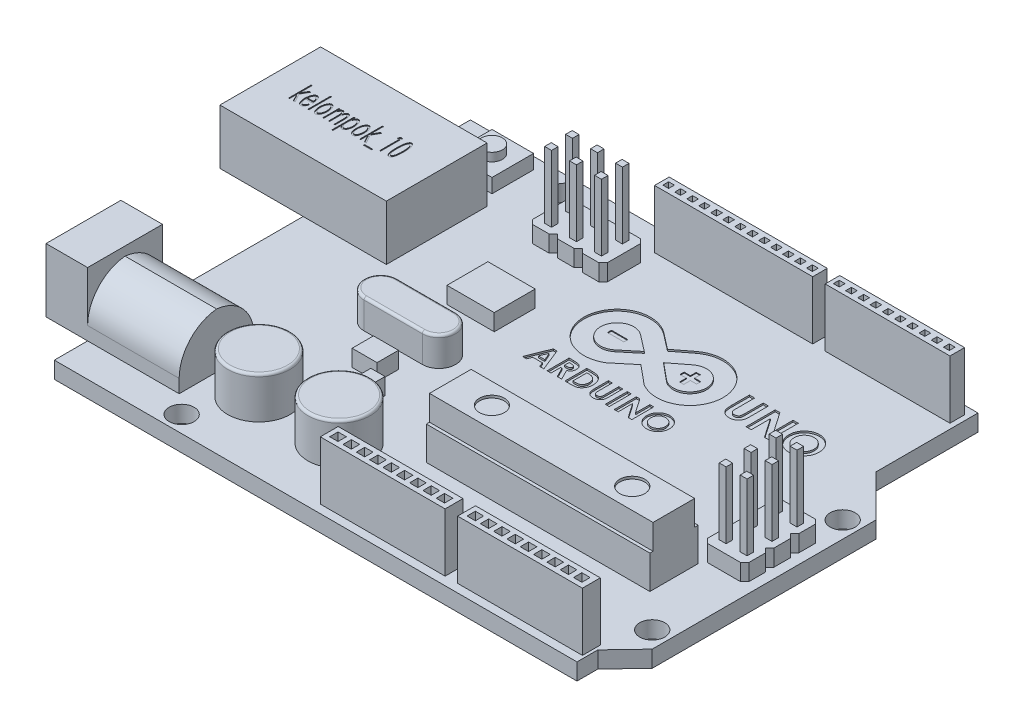
SolidWorks part; units mm, degrees
ref_plane "Front Plane" through (0, 0, 0) normal (0, 0, 1) x (1, 0, 0)
ref_plane "Top Plane" through (0, 0, 0) normal (0, 1, 0) x (1, 0, 0)
ref_plane "Right Plane" through (0, 0, 0) normal (1, 0, 0) x (0, 0, -1)
sketch "Sketch2" plane through (0, 0, 0) normal (0, 1, 0) x (1, 0, 0)
  line L0 (-33, 25) -> (33, -25) construction
  line L1 (-33, 25) -> (28, 25)
  line L2 (-33, 25) -> (-33, -25)
  line L3 (-33, -25) -> (29.8107, -25)
  line L4 (33, 7.74) -> (33, -19.15)
  line L5 (33, 25) -> (-33, -25) construction
  line L6 (28, 25) -> (28, 12.7479)
  line L7 (33, 7.74) -> (28, 12.7479)
  line L9 (29.8107, -25) -> (29.8107, -22.5)
  line L11 (33, -19.15) -> (29.8107, -22.5)
  dimension "D1" = 66
  dimension "D2" = 50
  dimension "D3" = 5
  dimension "D6" = 2.5
extrude "Boss-Extrude1" add sketch "Sketch2" along normal blind 2
sketch "Sketch3" plane through (0, 2, 0) normal (0, 1, 0) x (1, 0, 0)
  line L0 (28, 25) -> (-33, 25) construction
  line L1 (-33, 0) -> (33, 0) construction
  line L2 (-33, 25) -> (-33, -25) construction
  line L3 (33, -19.15) -> (33, 7.74) construction
  circle A0 centre (-19.7, 23) radius 1.5
  circle A1 centre (-19.7, -23) radius 1.5
  circle A2 centre (31, 5.74) radius 1.5
  circle A3 centre (31, -17.15) radius 1.5
  dimension "D1" = 3
  dimension "D2" = 2
  dimension "D4" = 3
  dimension "D5" = 2
  dimension "D6" = 2
  dimension "D7" = 3
  dimension "D3" = 13.3
  dimension "D8" = 2
extrude "Cut-Extrude2" cut sketch "Sketch3" against normal through all
sketch "Sketch4" plane through (0, 2, 0) normal (0, 1, 0) x (1, 0, 0)
  line L0 (-33, 25) -> (-33, -25) construction
  line L1 (-33, 17) -> (-23, 17)
  line L2 (-33, 17) -> (-33, 4.9)
  line L3 (-33, 4.9) -> (-23, 4.9)
  line L4 (-23, 17) -> (-23, 4.9)
  line L6 (-33, -12) -> (-22, -12)
  line L7 (-33, -12) -> (-33, -21)
  line L8 (-33, -21) -> (-22, -21)
  line L9 (-22, -12) -> (-22, -21)
  dimension "D1" = 8
  dimension "D2" = 12.1
  dimension "D3" = 10
  dimension "D4" = 4
  dimension "D5" = 9
  dimension "D6" = 11
extrude "Cut-Extrude3" cut sketch "Sketch4" against normal blind 0.4
sketch "Sketch5" plane through (0, 2, 0) normal (0, 1, 0) x (1, 0, 0)
  line L0 (27.2916, -0.8244) -> (26.7916, -0.3244)
  line L1 (31.2916, 2.1756) -> (27.2916, 2.1756)
  line L2 (31.7916, 1.6756) -> (31.7916, -0.3244)
  line L3 (31.2916, -0.8244) -> (27.2916, -0.8244)
  line L4 (26.7916, 1.6756) -> (26.7916, -0.3244)
  line L10 (27.2916, 2.1756) -> (26.7916, 1.6756)
  line L11 (31.2916, 2.1756) -> (31.7916, 1.6756)
  line L12 (31.2916, -0.8244) -> (31.7916, -0.3244)
extrude "Boss-Extrude2" add sketch "Sketch5" along normal blind 2
pattern_linear "LPattern1" count 3 spacing 3 along (0, 0, 1) of "Boss-Extrude2"
sketch "Sketch6" plane through (0, 4, 0) normal (0, 1, 0) x (1, 0, 0)
  line L1 (27.6416, 1.0456) -> (28.4716, 1.0456)
  line L2 (27.6416, 1.0456) -> (27.6416, 0.2556)
  line L3 (27.6416, 0.2556) -> (28.4716, 0.2556)
  line L4 (28.4716, 1.0456) -> (28.4716, 0.2556)
  dimension "D1" = 1.13
  dimension "D2" = 0.79
  dimension "D3" = 0.85
  dimension "D4" = 0.83
extrude "Boss-Extrude3" add sketch "Sketch6" along normal blind 8
pattern_linear "LPattern2" count 3 spacing 3 along (0, 0, 1) count 2 spacing 2.52 along (1, 0, 0) of "Boss-Extrude3"
sketch "Sketch7" plane through (0, 2, 0) normal (0, 1, 0) x (1, 0, 0)
  line L0 (28, 25) -> (-33, 25) construction
  line L1 (-16.41, 20.86) -> (-14.41, 20.86)
  line L2 (-16.91, 20.36) -> (-16.91, 16.36)
  line L3 (-16.41, 15.86) -> (-14.41, 15.86)
  line L4 (-13.91, 20.36) -> (-13.91, 16.36)
  line L5 (-33, 25) -> (-33, 17) construction
  line L6 (-13.91, 20.86) -> (-14.0975, 20.5475) construction
  line L7 (-16.91, 20.86) -> (-16.7225, 20.5475) construction
  line L10 (-16.41, 20.86) -> (-16.91, 20.36)
  line L11 (-14.41, 20.86) -> (-13.91, 20.36)
  line L12 (-16.41, 15.86) -> (-16.91, 16.36)
  line L13 (-14.41, 15.86) -> (-13.91, 16.36)
  line L14 (-14.0975, 16.1725) -> (-13.91, 15.86) construction
  line L15 (-16.7225, 16.1725) -> (-16.91, 15.86) construction
  point P6 (-16.91, 18.36)
  dimension "D1" = 4.14
  dimension "D2" = 16.09
  dimension "D3" = 3
  dimension "D4" = 5
  dimension "D5" = 0.5
  dimension "D6" = 0.5
extrude "Boss-Extrude4" add sketch "Sketch7" along normal blind 2
pattern_linear "LPattern3" count 3 spacing 3 along (1, 0, 0) of "Boss-Extrude4"
sketch "Sketch8" plane through (0, 4, 0) normal (0, 1, 0) x (1, 0, 0)
  line L0 (-14.41, 20.86) -> (-16.41, 20.86) construction
  line L1 (-15.78, 20.01) -> (-14.95, 20.01)
  line L2 (-15.78, 20.01) -> (-15.78, 19.22)
  line L3 (-15.78, 19.22) -> (-14.95, 19.22)
  line L4 (-14.95, 20.01) -> (-14.95, 19.22)
  line L5 (-16.91, 20.36) -> (-16.91, 16.36) construction
  dimension "D1" = 0.85
  dimension "D2" = 1.13
  dimension "D3" = 0.79
  dimension "D4" = 0.83
extrude "Boss-Extrude5" add sketch "Sketch8" along normal blind 8
pattern_linear "LPattern4" count 3 spacing 3 along (1, 0, 0) count 2 spacing 2.52 along (0, 0, 1) of "Boss-Extrude5"
sketch "Sketch13" plane through (0, 2, 0) normal (0, 1, 0) x (1, 0, 0)
  line L0 (-17.4291, -1.3426) -> (-10.4291, -1.3426) construction
  line L4 (-17.4291, 0.6574) -> (-10.4291, 0.6574)
  line L5 (-17.4291, -3.3426) -> (-10.4291, -3.3426)
  arc A2 (-17.4291, 0.6574) -> (-17.4291, -3.3426) centre (-17.4291, -1.3426) ccw
  arc A3 (-10.4291, -3.3426) -> (-10.4291, 0.6574) centre (-10.4291, -1.3426) ccw
  point P2 (-13.9291, -1.3426)
  dimension "D1" = 7
  dimension "D2" = 2
extrude "Boss-Extrude6" add sketch "Sketch13" along normal blind 3.5
fillet "Fillet4" radius 0.3 4 edges at (-19.4291, 5.5, 1.3426) (-13.9291, 5.5, -0.6574) (-8.4291, 5.5, 1.3426) (-13.9291, 5.5, 3.3426)
sketch "Sketch15" plane through (0, 2, 0) normal (0, 1, 0) x (1, 0, 0)
  line L1 (-15.1968, 9.2986) -> (-9.5153, 9.2986)
  line L2 (-15.1968, 9.2986) -> (-15.1968, 4.382)
  line L3 (-15.1968, 4.382) -> (-9.5153, 4.382)
  line L4 (-9.5153, 9.2986) -> (-9.5153, 4.382)
extrude "Boss-Extrude8" add sketch "Sketch15" along normal blind 2
sketch "Sketch17" plane through (0, 2, 0) normal (0, 1, 0) x (1, 0, 0)
  line L1 (-14.3468, -5.2998) -> (-11.349, -5.2998)
  line L2 (-14.3468, -5.2998) -> (-14.3468, -7.8693)
  line L3 (-14.3468, -7.8693) -> (-11.349, -7.8693)
  line L4 (-11.349, -5.2998) -> (-11.349, -7.8693)
extrude "Boss-Extrude9" add sketch "Sketch17" along normal blind 2
sketch "Sketch18" plane through (0, 2, 0) normal (0, 1, 0) x (1, 0, 0)
  line L1 (-11.1349, -8.8329) -> (-9.4218, -8.8329)
  line L2 (-11.1349, -8.8329) -> (-11.1349, -11.6167)
  line L3 (-11.1349, -11.6167) -> (-9.4218, -11.6167)
  line L4 (-9.4218, -8.8329) -> (-9.4218, -11.6167)
extrude "Boss-Extrude10" add sketch "Sketch18" along normal blind 2
sketch "Sketch20" plane through (0, 2, 0) normal (0, 1, 0) x (1, 0, 0)
  line L1 (-29.0149, 18.6084) -> (-24.0149, 18.6084)
  line L2 (-29.0149, 18.6084) -> (-29.0149, 23.6084)
  line L3 (-29.0149, 23.6084) -> (-24.0149, 23.6084)
  line L4 (-24.0149, 18.6084) -> (-24.0149, 23.6084)
  dimension "D1" = 5
  dimension "D2" = 5
extrude "Boss-Extrude11" add sketch "Sketch20" along normal blind 1.7
sketch "Sketch22" plane through (0, 3.7, 0) normal (0, 1, 0) x (1, 0, 0)
  line L0 (-29.0149, 21.1084) -> (-24.0149, 21.1084) construction
  line L1 (-29.0149, 23.6084) -> (-29.0149, 18.6084) construction
  line L2 (-24.0149, 18.6084) -> (-24.0149, 23.6084) construction
  circle A0 centre (-26.5149, 21.1084) radius 1.25
  dimension "D1" = 2.5
extrude "Boss-Extrude12" add sketch "Sketch22" along normal blind 1
sketch "Sketch23" plane through (0, 2, 0) normal (0, 1, 0) x (1, 0, 0)
  circle A0 centre (-16.9164, -16.5) radius 3.75
  dimension "D1" = 7.5
extrude "Boss-Extrude13" add sketch "Sketch23" along normal blind 5
sketch "Sketch24" plane through (0, 2, 0) normal (0, 1, 0) x (1, 0, 0)
  circle A0 centre (-7.2805, -16.5) radius 3.75
  dimension "D1" = 7.5
extrude "Boss-Extrude14" add sketch "Sketch24" along normal blind 5
fillet "Fillet5" radius 0.3 1 edges at (-7.2805, 7, 20.25)
fillet "Fillet6" radius 0.3 1 edges at (-16.9164, 7, 20.25)
sketch "Sketch25" plane through (0, 2, 0) normal (0, 1, 0) x (1, 0, 0)
  line L0 (-33, -25) -> (29.8107, -25) construction
  line L10 (-2.0383, -21.85) -> (12.9617, -21.85)
  line L11 (-2.0383, -21.85) -> (-2.0383, -24)
  line L12 (-2.0383, -24) -> (12.9617, -24)
  line L13 (12.9617, -21.85) -> (12.9617, -24)
  line L14 (14.4617, -21.85) -> (29.4617, -21.85)
  line L15 (14.4617, -21.85) -> (14.4617, -24)
  line L16 (14.4617, -24) -> (29.4617, -24)
  line L17 (29.4617, -21.85) -> (29.4617, -24)
  line L18 (12.3839, 24) -> (27.3839, 24)
  line L19 (-8.1161, 24) -> (10.8839, 24)
  line L20 (-8.1161, 24) -> (-8.1161, 22.2484)
  line L21 (-8.1161, 22.2484) -> (10.8839, 22.2484)
  line L22 (10.8839, 24) -> (10.8839, 22.2484)
  line L23 (12.3839, 24) -> (12.3839, 22.2484)
  line L24 (12.3839, 22.2484) -> (27.3839, 22.2484)
  line L25 (27.3839, 24) -> (27.3839, 22.2484)
  line L26 (28, 25) -> (-33, 25) construction
  dimension "D1" = 15
  dimension "D2" = 15
  dimension "D3" = 2.15
  dimension "D4" = 2.15
  dimension "D5" = 1.5
  dimension "D6" = 19
  dimension "D7" = 15
  dimension "D8" = 1
  dimension "D9" = 1
  dimension "D10" = 1
  dimension "D11" = 1.5
sketch "Sketch27" plane through (0, 2, 0) normal (0, 1, 0) x (1, 0, 0)
  line L0 (5.8645, 12.8775) -> (3.8851, 11.3504)
  line L1 (3.8851, 11.3504) -> (5.8095, 9.7545)
  line L2 (4.6428, 14.461) -> (2.7154, 12.9739)
  line L3 (2.7154, 9.774) -> (4.992, 7.886)
  line L7 (1.5456, 11.3504) -> (-0.3788, 9.7545)
  line L8 (-0.4338, 12.8775) -> (1.5456, 11.3504)
  line L10 (0.7879, 14.461) -> (2.7154, 12.9739)
  line L11 (2.7154, 9.774) -> (0.4387, 7.886)
  arc A0 (5.8095, 9.7545) -> (5.8645, 12.8775) centre (7.0862, 11.294) ccw
  arc A2 (4.992, 7.886) -> (4.6428, 14.461) centre (7.0862, 11.294) ccw
  arc A3 (-0.3788, 9.7545) -> (-0.4338, 12.8775) centre (-1.6555, 11.294) cw
  arc A4 (0.4387, 7.886) -> (0.7879, 14.461) centre (-1.6555, 11.294) cw
  text T0 "<b>ARDUINO</b>" font "Century Gothic" height in points 10
  point P2 (-5.6498, 11.5062)
  dimension "D1" = 4
  dimension "D2" = 2
  dimension "D3" = 2.5
  dimension "D4" = 2.5
  dimension "D5" = 8
extrude "Cut-Extrude5" cut sketch "Sketch27" against normal blind 0.2
sketch "Sketch29" plane through (0, 2, 0) normal (0, 1, 0) x (1, 0, 0)
  text T0 "<b>UNO</b>\r\n"
extrude "Cut-Extrude6" cut sketch "Sketch29" against normal blind 0.2
sketch "Sketch30" plane through (0, 2, 0) normal (0, 1, 0) x (1, 0, 0)
  line L1 (6.8413, 12.294) -> (7.3413, 12.294)
  line L2 (6.8413, 12.294) -> (6.8413, 11.6007)
  line L3 (6.8413, 10.294) -> (7.3413, 10.294)
  line L4 (7.3413, 12.294) -> (7.3413, 11.6007)
  line L5 (6.0863, 11.6007) -> (6.8413, 11.6007)
  line L6 (6.0863, 11.6007) -> (6.0863, 11.1007)
  line L7 (6.0863, 11.1007) -> (6.8413, 11.1007)
  line L8 (8.0863, 11.6007) -> (8.0863, 11.1007)
  line L9 (-2.6354, 11.5921) -> (-0.6721, 11.5921)
  line L10 (-2.6354, 11.5921) -> (-2.6354, 11.1188)
  line L11 (-2.6354, 11.1188) -> (-0.6721, 11.1188)
  line L12 (-0.6721, 11.5921) -> (-0.6721, 11.1188)
  line L13 (7.3413, 11.1007) -> (8.0863, 11.1007)
  line L14 (6.8413, 11.1007) -> (6.8413, 10.294)
  line L15 (7.3413, 11.1007) -> (7.3413, 10.294)
  line L17 (7.3413, 11.6007) -> (8.0863, 11.6007)
  dimension "D1" = 0.5
  dimension "D2" = 0.5
  dimension "D5" = 2
extrude "Cut-Extrude7" cut sketch "Sketch30" against normal blind 0.1
sketch "Sketch33" plane through (0, 1.6, 0) normal (0, 1, 0) x (1, 0, 0)
  line L1 (-33, 17) -> (-23, 17)
  line L2 (-33, 17) -> (-33, 4.9)
  line L3 (-33, 4.9) -> (-23, 4.9)
  line L4 (-23, 17) -> (-23, 4.9)
extrude "Boss-Extrude17" add sketch "Sketch33" along normal blind 7 contours L2 L1 L4 L3
sketch "Sketch35" plane through (-33, 0, 0) normal (-1, 0, 0) x (0, 0, 1)
  line L1 (-17, 8.6) -> (-4.9, 8.6)
  line L2 (-17, 8.6) -> (-17, 2)
  line L3 (-17, 2) -> (-4.9, 2)
  line L4 (-4.9, 8.6) -> (-4.9, 2)
extrude "Boss-Extrude18" add sketch "Sketch35" along normal blind 10
sketch "Sketch36" plane through (0, 1.6, 0) normal (0, 1, 0) x (1, 0, 0)
  line L1 (-33, -12) -> (-22, -12)
  line L2 (-33, -12) -> (-33, -21)
  line L3 (-33, -21) -> (-22, -21)
  line L4 (-22, -12) -> (-22, -21)
extrude "Boss-Extrude19" add sketch "Sketch36" along normal blind 7
sketch "Sketch37" plane through (-33, 0, 0) normal (-1, 0, 0) x (0, 0, 1)
  line L1 (12, 2) -> (21, 2)
  line L2 (12, 2) -> (12, 8.6)
  line L3 (12, 8.6) -> (21, 8.6)
  line L4 (21, 2) -> (21, 8.6)
extrude "Boss-Extrude20" add sketch "Sketch37" against normal blind 1
fillet "Fillet8" radius 5 2 edges at (-27.5, 8.6, 12) (-27.5, 8.6, 21)
sketch "Sketch47" plane through (-33, 0, 0) normal (-1, 0, 0) x (0, 0, 1)
  line L0 (21, 3.6) -> (21, 2) construction
  line L1 (12, 2) -> (21, 2)
  line L2 (12, 2) -> (12, 9.6357)
  line L3 (12, 9.6357) -> (21, 9.6357)
  line L4 (21, 2) -> (21, 9.6357)
extrude "Boss-Extrude23" add sketch "Sketch47" along normal blind 5
sketch "Sketch48" plane through (-38, 0, 0) normal (-1, 0, 0) x (0, 0, 1)
  circle A0 centre (16.5, 5.8178) radius 2.6874
extrude "Cut-Extrude14" cut sketch "Sketch48" against normal blind 8
sketch "Sketch49" plane through (-30, 0, 0) normal (-1, 0, 0) x (0, 0, 1)
  circle A0 centre (16.5, 5.8178) radius 0.2092
extrude "Boss-Extrude24" add sketch "Sketch49" along normal blind 5.5
fillet "Fillet16" radius 0.1 1 edges at (-35.5, 5.8178, 16.7092)
sketch "Sketch54" plane through (-43, 0, 0) normal (-1, 0, 0) x (0, 0, 1)
  line L0 (-14.5, 6.4502) -> (-13.4359, 7.7502)
  line L2 (-14.5, 6.4502) -> (-14.5, 3.0635)
  line L3 (-14.5, 3.0635) -> (-7.4, 3.0635)
  line L4 (-7.4, 6.4502) -> (-7.4, 3.0635)
  line L5 (-13.4359, 7.7502) -> (-8.4359, 7.7502)
  line L6 (-8.4359, 7.7502) -> (-7.4, 6.4502)
  line L7 (-17, 8.6) -> (-17, 2) construction
  line L8 (-4.9, 2) -> (-4.9, 8.6) construction
  dimension "D1" = 2.5
  dimension "D2" = 2.5
  dimension "D4" = 5
  dimension "D5" = 1.68
extrude "Cut-Extrude15" cut sketch "Sketch54" against normal blind 6
sketch "Sketch55" plane through (-37, 0, 0) normal (-1, 0, 0) x (0, 0, 1)
  line L0 (-14.5, 6.4502) -> (-14.5, 3.0635) construction
  line L1 (-12.4955, 5.6822) -> (-9.4, 5.6822)
  line L2 (-12.4955, 5.6822) -> (-12.4955, 4.7075)
  line L3 (-12.4955, 4.7075) -> (-9.4, 4.7075)
  line L4 (-9.4, 5.6822) -> (-9.4, 4.7075)
  line L5 (-7.4, 3.0635) -> (-7.4, 6.4502) construction
  dimension "D1" = 2.0045
  dimension "D2" = 2
extrude "Boss-Extrude25" add sketch "Sketch55" along normal blind 6
extrude "Boss-Extrude26" add sketch "Sketch25" along normal blind 7
sketch "Sketch57" plane through (0, 9, 0) normal (0, 1, 0) x (1, 0, 0)
  line L0 (-6.214, 23.4742) -> (-6.214, 22.7742)
  line L1 (-7.654, 23.4742) -> (-6.954, 23.4742)
  line L2 (-7.654, 23.4742) -> (-7.654, 22.7742)
  line L3 (-7.654, 22.7742) -> (-6.954, 22.7742)
  line L4 (-6.954, 23.4742) -> (-6.954, 22.7742)
  line L5 (-6.214, 23.4742) -> (-5.514, 23.4742)
  line L6 (-5.514, 23.4742) -> (-5.514, 22.7742)
  line L7 (-6.214, 22.7742) -> (-5.514, 22.7742)
  line L8 (-4.774, 23.4742) -> (-4.774, 22.7742)
  line L9 (-4.774, 23.4742) -> (-4.074, 23.4742)
  line L10 (-4.074, 23.4742) -> (-4.074, 22.7742)
  line L11 (-4.774, 22.7742) -> (-4.074, 22.7742)
  line L12 (-3.334, 23.4742) -> (-3.334, 22.7742)
  line L13 (-3.334, 23.4742) -> (-2.634, 23.4742)
  line L14 (-2.634, 23.4742) -> (-2.634, 22.7742)
  line L15 (-3.334, 22.7742) -> (-2.634, 22.7742)
  line L16 (-1.894, 23.4742) -> (-1.894, 22.7742)
  line L17 (-1.894, 23.4742) -> (-1.194, 23.4742)
  line L18 (-1.194, 23.4742) -> (-1.194, 22.7742)
  line L19 (-1.894, 22.7742) -> (-1.194, 22.7742)
  line L20 (-0.454, 23.4742) -> (-0.454, 22.7742)
  line L21 (-0.454, 23.4742) -> (0.246, 23.4742)
  line L22 (0.246, 23.4742) -> (0.246, 22.7742)
  line L23 (-0.454, 22.7742) -> (0.246, 22.7742)
  line L24 (0.986, 23.4742) -> (0.986, 22.7742)
  line L25 (0.986, 23.4742) -> (1.686, 23.4742)
  line L26 (1.686, 23.4742) -> (1.686, 22.7742)
  line L27 (0.986, 22.7742) -> (1.686, 22.7742)
  line L28 (2.426, 23.4742) -> (2.426, 22.7742)
  line L29 (2.426, 23.4742) -> (3.126, 23.4742)
  line L30 (3.126, 23.4742) -> (3.126, 22.7742)
  line L31 (2.426, 22.7742) -> (3.126, 22.7742)
  line L32 (3.866, 23.4742) -> (3.866, 22.7742)
  line L33 (3.866, 23.4742) -> (4.566, 23.4742)
  line L34 (4.566, 23.4742) -> (4.566, 22.7742)
  line L35 (3.866, 22.7742) -> (4.566, 22.7742)
  line L36 (5.306, 23.4742) -> (5.306, 22.7742)
  line L37 (5.306, 23.4742) -> (6.006, 23.4742)
  line L38 (6.006, 23.4742) -> (6.006, 22.7742)
  line L39 (5.306, 22.7742) -> (6.006, 22.7742)
  line L40 (6.746, 23.4742) -> (6.746, 22.7742)
  line L41 (6.746, 23.4742) -> (7.446, 23.4742)
  line L42 (7.446, 23.4742) -> (7.446, 22.7742)
  line L43 (6.746, 22.7742) -> (7.446, 22.7742)
  line L44 (8.186, 23.4742) -> (8.186, 22.7742)
  line L45 (8.186, 23.4742) -> (8.886, 23.4742)
  line L46 (8.886, 23.4742) -> (8.886, 22.7742)
  line L47 (8.186, 22.7742) -> (8.886, 22.7742)
  line L48 (9.626, 23.4742) -> (9.626, 22.7742)
  line L49 (9.626, 23.4742) -> (10.326, 23.4742)
  line L50 (10.326, 23.4742) -> (10.326, 22.7742)
  line L51 (9.626, 22.7742) -> (10.326, 22.7742)
  dimension "D1" = 0.7
  dimension "D2" = 0.7
  dimension "D3" = 0.7
  dimension "D4" = 0.7
  dimension "D5" = 13
extrude "Cut-Extrude17" cut sketch "Sketch57" against normal blind 6
sketch "Sketch58" plane through (0, 9, 0) normal (0, 1, 0) x (1, 0, 0)
  line L0 (14.316, 23.4742) -> (14.316, 22.7742)
  line L1 (12.846, 23.4742) -> (13.546, 23.4742)
  line L2 (12.846, 23.4742) -> (12.846, 22.7742)
  line L3 (12.846, 22.7742) -> (13.546, 22.7742)
  line L4 (13.546, 23.4742) -> (13.546, 22.7742)
  line L5 (14.316, 23.4742) -> (15.016, 23.4742)
  line L6 (15.016, 23.4742) -> (15.016, 22.7742)
  line L7 (14.316, 22.7742) -> (15.016, 22.7742)
  line L8 (15.786, 23.4742) -> (15.786, 22.7742)
  line L9 (15.786, 23.4742) -> (16.486, 23.4742)
  line L10 (16.486, 23.4742) -> (16.486, 22.7742)
  line L11 (15.786, 22.7742) -> (16.486, 22.7742)
  line L12 (17.256, 23.4742) -> (17.256, 22.7742)
  line L13 (17.256, 23.4742) -> (17.956, 23.4742)
  line L14 (17.956, 23.4742) -> (17.956, 22.7742)
  line L15 (17.256, 22.7742) -> (17.956, 22.7742)
  line L16 (18.726, 23.4742) -> (18.726, 22.7742)
  line L17 (18.726, 23.4742) -> (19.426, 23.4742)
  line L18 (19.426, 23.4742) -> (19.426, 22.7742)
  line L19 (18.726, 22.7742) -> (19.426, 22.7742)
  line L20 (20.196, 23.4742) -> (20.196, 22.7742)
  line L21 (20.196, 23.4742) -> (20.896, 23.4742)
  line L22 (20.896, 23.4742) -> (20.896, 22.7742)
  line L23 (20.196, 22.7742) -> (20.896, 22.7742)
  line L24 (21.666, 23.4742) -> (21.666, 22.7742)
  line L25 (21.666, 23.4742) -> (22.366, 23.4742)
  line L26 (22.366, 23.4742) -> (22.366, 22.7742)
  line L27 (21.666, 22.7742) -> (22.366, 22.7742)
  line L28 (23.136, 23.4742) -> (23.136, 22.7742)
  line L29 (23.136, 23.4742) -> (23.836, 23.4742)
  line L30 (23.836, 23.4742) -> (23.836, 22.7742)
  line L31 (23.136, 22.7742) -> (23.836, 22.7742)
  line L32 (24.606, 23.4742) -> (24.606, 22.7742)
  line L33 (24.606, 23.4742) -> (25.306, 23.4742)
  line L34 (25.306, 23.4742) -> (25.306, 22.7742)
  line L35 (24.606, 22.7742) -> (25.306, 22.7742)
  line L36 (26.076, 23.4742) -> (26.076, 22.7742)
  line L37 (26.076, 23.4742) -> (26.776, 23.4742)
  line L38 (26.776, 23.4742) -> (26.776, 22.7742)
  line L39 (26.076, 22.7742) -> (26.776, 22.7742)
  dimension "D1" = 0.7
  dimension "D2" = 0.7
  dimension "D3" = 0.7
  dimension "D4" = 0.7
  dimension "D5" = 10
extrude "Cut-Extrude18" cut sketch "Sketch58" against normal blind 6
sketch "Sketch59" plane through (0, 9, 0) normal (0, 1, 0) x (1, 0, 0)
  line L0 (0.118, -22.425) -> (0.118, -23.425)
  line L1 (-1.482, -22.425) -> (-0.482, -22.425)
  line L2 (-1.482, -22.425) -> (-1.482, -23.425)
  line L3 (-1.482, -23.425) -> (-0.482, -23.425)
  line L4 (-0.482, -22.425) -> (-0.482, -23.425)
  line L5 (0.118, -22.425) -> (1.118, -22.425)
  line L6 (1.118, -22.425) -> (1.118, -23.425)
  line L7 (0.118, -23.425) -> (1.118, -23.425)
  line L8 (1.718, -22.425) -> (1.718, -23.425)
  line L9 (1.718, -22.425) -> (2.718, -22.425)
  line L10 (2.718, -22.425) -> (2.718, -23.425)
  line L11 (1.718, -23.425) -> (2.718, -23.425)
  line L12 (3.318, -22.425) -> (3.318, -23.425)
  line L13 (3.318, -22.425) -> (4.318, -22.425)
  line L14 (4.318, -22.425) -> (4.318, -23.425)
  line L15 (3.318, -23.425) -> (4.318, -23.425)
  line L16 (4.918, -22.425) -> (4.918, -23.425)
  line L17 (4.918, -22.425) -> (5.918, -22.425)
  line L18 (5.918, -22.425) -> (5.918, -23.425)
  line L19 (4.918, -23.425) -> (5.918, -23.425)
  line L20 (6.518, -22.425) -> (6.518, -23.425)
  line L21 (6.518, -22.425) -> (7.518, -22.425)
  line L22 (7.518, -22.425) -> (7.518, -23.425)
  line L23 (6.518, -23.425) -> (7.518, -23.425)
  line L24 (8.118, -22.425) -> (8.118, -23.425)
  line L25 (8.118, -22.425) -> (9.118, -22.425)
  line L26 (9.118, -22.425) -> (9.118, -23.425)
  line L27 (8.118, -23.425) -> (9.118, -23.425)
  line L28 (9.718, -22.425) -> (9.718, -23.425)
  line L29 (9.718, -22.425) -> (10.718, -22.425)
  line L30 (10.718, -22.425) -> (10.718, -23.425)
  line L31 (9.718, -23.425) -> (10.718, -23.425)
  line L32 (11.318, -22.425) -> (11.318, -23.425)
  line L33 (11.318, -22.425) -> (12.318, -22.425)
  line L34 (12.318, -22.425) -> (12.318, -23.425)
  line L35 (11.318, -23.425) -> (12.318, -23.425)
  dimension "D1" = 0.8
  dimension "D2" = 0.8
  dimension "D3" = 1
  dimension "D4" = 1
  dimension "D5" = 9
extrude "Cut-Extrude19" cut sketch "Sketch59" against normal blind 6
sketch "Sketch60" plane through (0, 9, 0) normal (0, 1, 0) x (1, 0, 0)
  line L0 (16.618, -22.425) -> (16.618, -23.425)
  line L1 (15.018, -22.425) -> (16.018, -22.425)
  line L2 (15.018, -22.425) -> (15.018, -23.425)
  line L3 (15.018, -23.425) -> (16.018, -23.425)
  line L4 (16.018, -22.425) -> (16.018, -23.425)
  line L5 (16.618, -22.425) -> (17.618, -22.425)
  line L6 (17.618, -22.425) -> (17.618, -23.425)
  line L7 (16.618, -23.425) -> (17.618, -23.425)
  line L8 (18.218, -22.425) -> (18.218, -23.425)
  line L9 (18.218, -22.425) -> (19.218, -22.425)
  line L10 (19.218, -22.425) -> (19.218, -23.425)
  line L11 (18.218, -23.425) -> (19.218, -23.425)
  line L12 (19.818, -22.425) -> (19.818, -23.425)
  line L13 (19.818, -22.425) -> (20.818, -22.425)
  line L14 (20.818, -22.425) -> (20.818, -23.425)
  line L15 (19.818, -23.425) -> (20.818, -23.425)
  line L16 (21.418, -22.425) -> (21.418, -23.425)
  line L17 (21.418, -22.425) -> (22.418, -22.425)
  line L18 (22.418, -22.425) -> (22.418, -23.425)
  line L19 (21.418, -23.425) -> (22.418, -23.425)
  line L20 (23.018, -22.425) -> (23.018, -23.425)
  line L21 (23.018, -22.425) -> (24.018, -22.425)
  line L22 (24.018, -22.425) -> (24.018, -23.425)
  line L23 (23.018, -23.425) -> (24.018, -23.425)
  line L24 (24.618, -22.425) -> (24.618, -23.425)
  line L25 (24.618, -22.425) -> (25.618, -22.425)
  line L26 (25.618, -22.425) -> (25.618, -23.425)
  line L27 (24.618, -23.425) -> (25.618, -23.425)
  line L28 (26.218, -22.425) -> (26.218, -23.425)
  line L29 (26.218, -22.425) -> (27.218, -22.425)
  line L30 (27.218, -22.425) -> (27.218, -23.425)
  line L31 (26.218, -23.425) -> (27.218, -23.425)
  line L32 (27.818, -22.425) -> (27.818, -23.425)
  line L33 (27.818, -22.425) -> (28.818, -22.425)
  line L34 (28.818, -22.425) -> (28.818, -23.425)
  line L35 (27.818, -23.425) -> (28.818, -23.425)
  dimension "D1" = 0.8
  dimension "D2" = 0.8
  dimension "D3" = 1
  dimension "D4" = 1
  dimension "D5" = 9
extrude "Cut-Extrude20" cut sketch "Sketch60" against normal blind 6
sketch "Sketch61" plane through (0, 2, 0) normal (0, 1, 0) x (1, 0, 0)
  line L1 (0, -7.4971) -> (26.8656, -7.4971)
  line L2 (0, -7.4971) -> (0, -13.2974)
  line L3 (0, -13.2974) -> (26.8656, -13.2974)
  line L4 (26.8656, -7.4971) -> (26.8656, -13.2974)
extrude "Boss-Extrude27" add sketch "Sketch61" along normal blind 4
sketch "Sketch62" plane through (0, 6, 0) normal (0, 1, 0) x (1, 0, 0)
  line L0 (0, -7.4971) -> (0, -13.2974) construction
  line L1 (0, -7.9148) -> (26.8656, -7.9148)
  line L2 (0, -7.9148) -> (0, -12.9166)
  line L3 (0, -12.9166) -> (26.8656, -12.9166)
  line L4 (26.8656, -7.9148) -> (26.8656, -12.9166)
  line L5 (26.8656, -13.2974) -> (26.8656, -7.4971) construction
extrude "Boss-Extrude28" add sketch "Sketch62" along normal blind 3
sketch "Sketch63" plane through (0, 9, 0) normal (0, 1, 0) x (1, 0, 0)
  line L0 (0, -7.4971) -> (0, -13.2974) construction
  line L1 (26.8656, -12.9166) -> (26.8656, -7.9148) construction
  circle A0 centre (5, -10.4157) radius 1.5
  circle A1 centre (21.8656, -10.4157) radius 1.5
  dimension "D1" = 5
  dimension "D2" = 5
  dimension "D3" = 3
  dimension "D4" = 3
extrude "Cut-Extrude21" cut sketch "Sketch63" against normal blind 0.3
sketch "Sketch64" plane through (0, 8.6, 0) normal (0, 1, 0) x (1, 0, 0)
  text T0 "kelompok_10" font "Century Gothic" height in points 10
extrude "Cut-Extrude22" cut sketch "Sketch64" against normal blind 0.1
